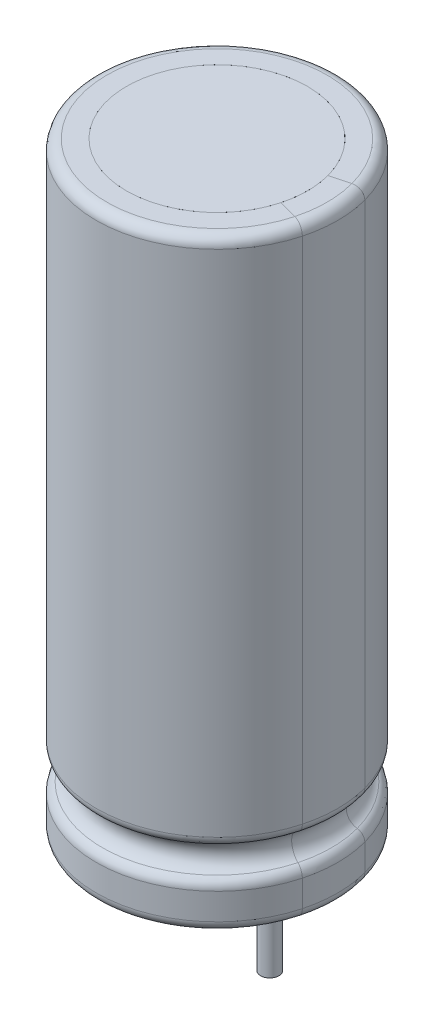
SolidWorks part; units mm, degrees
ref_plane "Alzado" through (0, 0, 0) normal (0, 0, 1) x (1, 0, 0)
ref_plane "Planta" through (0, 0, 0) normal (0, 1, 0) x (1, 0, 0)
ref_plane "Vista lateral" through (0, 0, 0) normal (1, 0, 0) x (0, 0, -1)
sketch "Croquis1" plane through (0, 0, 0) normal (0, 1, 0) x (1, 0, 0)
  line L1 (2.8978, 0.7765) -> (3.8637, 1.0353)
  line L2 (2.8978, -0.7765) -> (3.8637, -1.0353)
  circle A0 centre (0, 0) radius 4
  circle A1 centre (0, 0) radius 3
  dimension "D1" = 8
  dimension "D2" = 6
extrude "Saliente-Extruir3" add sketch "Croquis1" along normal blind 20 contours A1 L2 A0 L1 region at (3.4837, 0, 0)
extrude "Saliente-Extruir4" add sketch "Croquis1<5>" along normal blind 20 separate body contours A1 region at (0, 0, 0)
sketch "Croquis1<5>" plane through (0, 0, 0) normal (0, 1, 0) x (1, 0, 0) same geometry as "Croquis1"
extrude "Saliente-Extruir5" add sketch "Croquis1<6>" along normal blind 20 separate body contours A1 L1 A0 L2 region at (-3.1122, 0, 0)
sketch "Croquis1<6>" plane through (0, 0, 0) normal (0, 1, 0) x (1, 0, 0) same geometry as "Croquis1"
sketch "Croquis3" plane through (0, 0, 0) normal (1, 0, 0) x (0, 0, -1)
  line L0 (0, -1.736) -> (0, 22.3491)
  line L1 (-4, 20) -> (-4, 0) construction
  line L2 (-4, 0) -> (4, 0) construction
  circle A0 centre (-4, 2) radius 0.5
  dimension "D1" = 2
revolve "Cortar-Revolución1" cut sketch "Croquis3" angle 360 about L0
fillet "Redondeo1" radius 0.35 4 edges at (-4, 0, 0) (-4, 1.5, 0) (-4, 2.5, 0) (-4, 20, 0)
fillet "Redondeo2" radius 0.35 4 edges at (4, 0, 0) (4, 1.5, 0) (4, 2.5, 0) (4, 20, 0)
sketch "Croquis4" plane through (0, 0, 0) normal (0, -1, 0) x (1, 0, 0)
  circle A1 centre (-1.75, 0) radius 0.3011
  circle A2 centre (1.75, 0) radius 0.303
extrude "Saliente-Extruir6" add sketch "Croquis4" along normal blind 3 separate body contours A2 | A1
